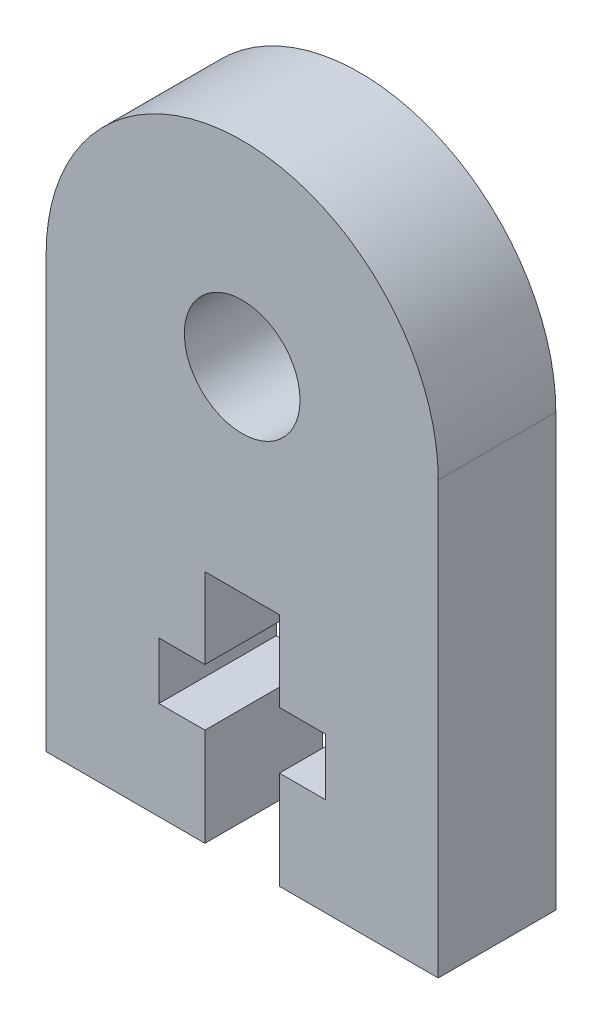
SolidWorks part; units mm, degrees
material "ABS"
ref_plane "Front Plane" through (0, 0, 0) normal (0, 0, 1) x (1, 0, 0)
ref_plane "Top Plane" through (0, 0, 0) normal (0, 1, 0) x (1, 0, 0)
ref_plane "Right Plane" through (0, 0, 0) normal (1, 0, 0) x (0, 0, -1)
sketch "Sketch1" plane through (0, 0, 0) normal (0, 0, 1) x (1, 0, 0)
  line L0 (0, 0) -> (-2.086, 2.086) construction
  line L1 (0, 0) -> (0, 2.95) construction
  line L2 (-10, 0) -> (-10, -22)
  line L3 (-10, -22) -> (10, -22)
  line L4 (10, -22) -> (10, 0)
  line L5 (0, 0) -> (0, -22) construction
  circle A0 centre (0, 0) radius 2.95
  arc A1 (-10, 0) -> (10, 0) centre (0, 0) cw
  dimension "D1" = 5.9
  dimension "D4" = 45
  dimension "D5" = 22
  dimension "D6" = 20
extrude "Boss-Extrude1" add sketch "Sketch1" along normal blind 6
sketch "Sketch3" plane through (0, 0, 6) normal (0, 0, 1) x (1, 0, 0)
  line L0 (-10, -22) -> (10, -22) construction
  line L1 (-1.9, -22) -> (1.9, -22)
  line L2 (-1.9, -22) -> (-1.9, -17)
  line L3 (-1.9, -10) -> (1.9, -10)
  line L4 (1.9, -22) -> (1.9, -17)
  line L5 (0, -10) -> (0, 0) construction
  line L6 (1.9, -14.1) -> (4.25, -14.1)
  line L7 (-4.25, -14.1) -> (-1.9, -14.1)
  line L8 (-4.25, -14.1) -> (-4.25, -17)
  line L9 (-4.25, -17) -> (-1.9, -17)
  line L10 (4.25, -14.1) -> (4.25, -17)
  line L11 (-1.9, -14.1) -> (-1.9, -10)
  line L12 (1.9, -17) -> (4.25, -17)
  line L13 (1.9, -14.1) -> (1.9, -10)
  point P18 (-3.075, -17)
  dimension "D1" = 3.8
  dimension "D3" = 12
  dimension "D4" = 8.5
  dimension "D5" = 2.9
  dimension "D6" = 5
extrude "Cut-Extrude2" cut sketch "Sketch3" against normal through all
equation "\"smallPulleyTeeth\"= 15"
equation "\"largePulleyTeeth\"= 30"
equation "\"eighthThick\"= 2.9mm"
equation "\"sixteenthThick\" = 1.7mm"
equation "\"quarterThick\"=6.0mm"
equation "\"OD\" = 146mm"
equation "\"puckAngle\" = 60.5deg"
equation "\"puckDiam\" = 76.5mm"
equation "\"axlePress\" = 5.9mm"
equation "\"D1@Sketch1\"=\"axlePress\""
equation "\"D1@Boss-Extrude1\"=\"quarterThick\""
equation "\"press\" = 0.2mm"
equation "\"wheelClear\" = 0.3mm"
equation "\"10-32clear\" = 4.8mm"
equation "\"D1@Sketch3\"=\"8-32clear\"-\"press\""
equation "\"6-32clear\" = 3.3mm"
equation "\"8-32clear\" = 4.0mm"
equation "\"wheelHeight\" = 22mm"
equation "\"D5@Sketch1\"=\"wheelHeight\""
equation "\"wheelWell\" = 65mm"
